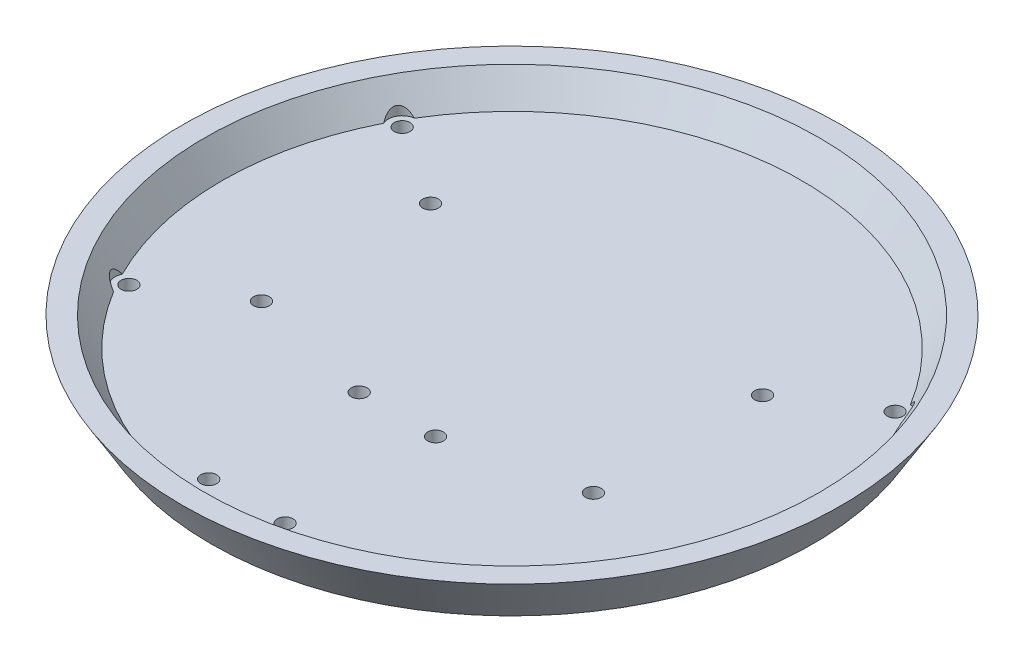
SolidWorks part; units mm, degrees
ref_plane "Front Plane" through (0, 0, 0) normal (0, 0, 1) x (1, 0, 0)
ref_plane "Top Plane" through (0, 0, 0) normal (0, 1, 0) x (1, 0, 0)
ref_plane "Right Plane" through (0, 0, 0) normal (1, 0, 0) x (0, 0, -1)
sketch "Sketch1" plane through (0, 0, 0) normal (0, 0, 1) x (1, 0, 0)
  line L0 (0, -4) -> (63, -4)
  line L1 (63, -4) -> (69, 6)
  line L6 (0, 0) -> (60.7352, 0)
  line L7 (60.7352, 0) -> (64.3352, 6)
  line L8 (69, 6) -> (64.3352, 6)
  line L9 (0, -4) -> (0, 0)
  line L10 (60.7352, 0) -> (65.57, 8.058) construction
  dimension "D1" = 69
  dimension "D2" = 63
  dimension "D3" = 10
  dimension "D4" = 4
revolve "Revolve1" add sketch "Sketch1" angle 360 about L9
sketch "Sketch4" plane through (0, 0, 0) normal (0, 1, 0) x (1, 0, 0)
  line L0 (-60.7352, 0) -> (60.7352, 0) construction
  line L1 (0, 60.7352) -> (0, -60.7352) construction
  line L2 (0, 0) -> (34.7493, 17.7056) construction
  line L3 (0, 0) -> (51.6026, 28.6038) construction
  circle A0 centre (0, 0) radius 60.7352 construction
  circle A1 centre (34.7493, 17.7056) radius 1.65
  circle A2 centre (51.6026, 28.6038) radius 1.65
  circle A4 centre (51.6026, -28.6038) radius 1.65
  circle A5 centre (34.7493, -17.7056) radius 1.65
  circle A6 centre (-34.7493, -17.7056) radius 1.65
  circle A7 centre (-51.6026, -28.6038) radius 1.65
  circle A8 centre (-51.6026, 28.6038) radius 1.65
  circle A9 centre (-34.7493, 17.7056) radius 1.65
  dimension "D5" = 3.3
  dimension "D6" = 3.3
  dimension "D1" = 27
  dimension "D2" = 29
  dimension "D3" = 39
  dimension "D4" = 59
extrude "Cut-Extrude1" cut sketch "Sketch4" against normal through all
sketch "Sketch5" plane through (0, 0, 0) normal (0, 1, 0) x (1, 0, 0)
  circle A0 centre (51.6026, 28.6038) radius 2.9
  circle A1 centre (51.6026, -28.6038) radius 2.9
  circle A2 centre (-51.6026, -28.6038) radius 2.9
  circle A3 centre (-51.6026, 28.6038) radius 2.9
  dimension "D1" = 5.8
extrude "Cut-Extrude2" cut sketch "Sketch5" along normal through all
sketch "Sketch6" plane through (0, 0, 0) normal (0, 1, 0) x (1, 0, 0)
  line L0 (8, -55.5) -> (-8, -55.5) construction
  circle A0 centre (8, -55.5) radius 1.65
  circle A1 centre (-8, -55.5) radius 1.65
  circle A2 centre (8, -24) radius 1.65
  circle A3 centre (-8, -24) radius 1.65
  point P8 (0, -55.5)
  point P10 (0, 0)
  dimension "D1" = 16
  dimension "D2" = 3.3
  dimension "D3" = 31.5
  dimension "D4" = 55.5
extrude "Cut-Extrude3" cut sketch "Sketch6" against normal through all
